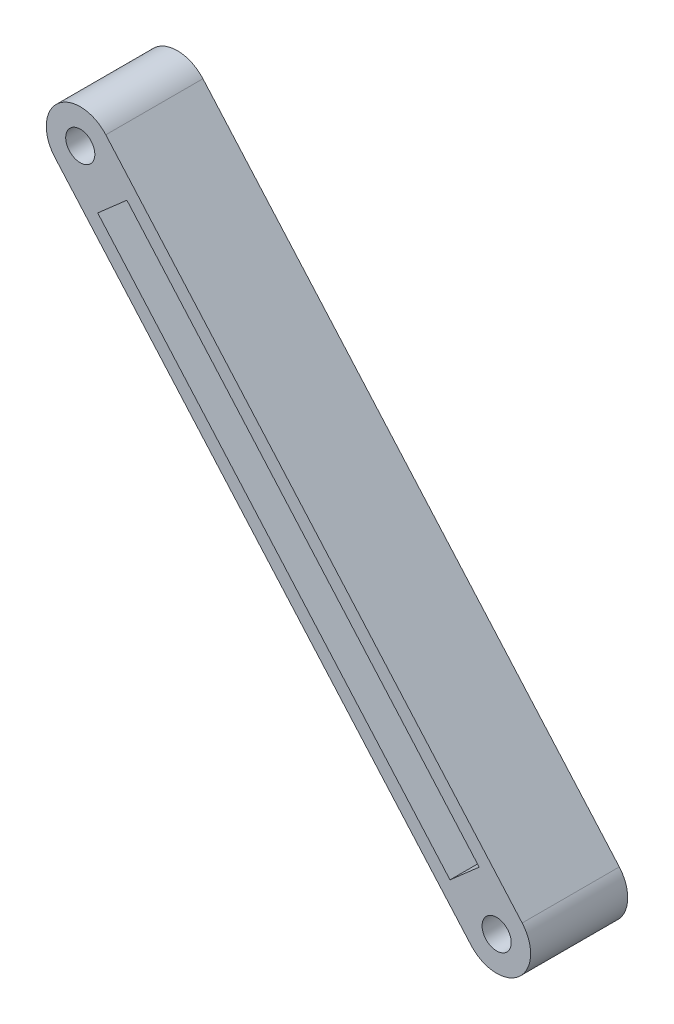
SolidWorks part; units mm, degrees
ref_plane "Front Plane" through (0, 0, 0) normal (0, 0, 1) x (1, 0, 0)
ref_plane "Top Plane" through (0, 0, 0) normal (0, 1, 0) x (1, 0, 0)
ref_plane "Right Plane" through (0, 0, 0) normal (1, 0, 0) x (0, 0, -1)
sketch "Sketch1" plane through (0, 0, 0) normal (0, 0, 1) x (1, 0, 0)
  line L0 (-145.7527, 107.7061) -> (-60, 10) construction
  line L1 (-145.7527, 107.7061) -> (-60, 10) construction
  line L2 (-151.0138, 103.0886) -> (-65.2611, 5.3825)
  line L3 (-140.4916, 112.3235) -> (-54.7389, 14.6175)
  circle A0 centre (-145.7527, 107.7061) radius 3 construction
  circle A1 centre (-145.7527, 107.7061) radius 3
  circle A2 centre (-60, 10) radius 3 construction
  circle A3 centre (-60, 10) radius 3
  circle A4 centre (-145.7527, 107.7061) radius 7
  circle A5 centre (-60, 10) radius 7
  dimension "D1" = 14
  dimension "D2" = 14
extrude "Boss-Extrude1" add sketch "Sketch1" along normal blind 10 and the other way blind 10 contours L1 A4 A5 | A4 L1 A5 | A1 A4 | A5 A3 region at (-146.1949, 100.9185, 0) region at (-100.209, 61.194, 0) region at (-105.5436, 56.5121, 0) region at (-59.5577, 16.7876, 0)
sketch "Sketch3" plane through (0, 0, 0) normal (0, 0, 1) x (1, 0, 0)
  line L0 (-142.1627, 97.5517) -> (-136.15, 102.8288)
  line L1 (-142.1627, 97.5517) -> (-69.6027, 14.8773)
  line L2 (-136.15, 102.8288) -> (-63.59, 20.1544)
  line L3 (-69.6027, 14.8773) -> (-63.59, 20.1544)
  line L4 (-140.4916, 112.3235) -> (-54.7389, 14.6175) construction
  line L5 (-151.0138, 103.0886) -> (-65.2611, 5.3825) construction
  circle A0 centre (-60, 10) radius 3 construction
  circle A1 centre (-145.7527, 107.7061) radius 3 construction
  dimension "D1" = 3
  dimension "D2" = 3
  dimension "D3" = 10
  dimension "D4" = 10
extrude "Cut-Extrude1" cut sketch "Sketch3" against normal up to surface (10 mm away) from offset 1.5 up to face at (-102.8763, 58.853, -10) offset against normal yes
extrude "Cut-Extrude2" cut sketch "Sketch3<2>" along normal up to surface (10 mm away) from offset 1.5 up to face at (-102.8763, 58.853, 10)
sketch "Sketch3<2>" plane through (0, 0, 0) normal (0, 0, 1) x (1, 0, 0) same geometry as "Sketch3"
